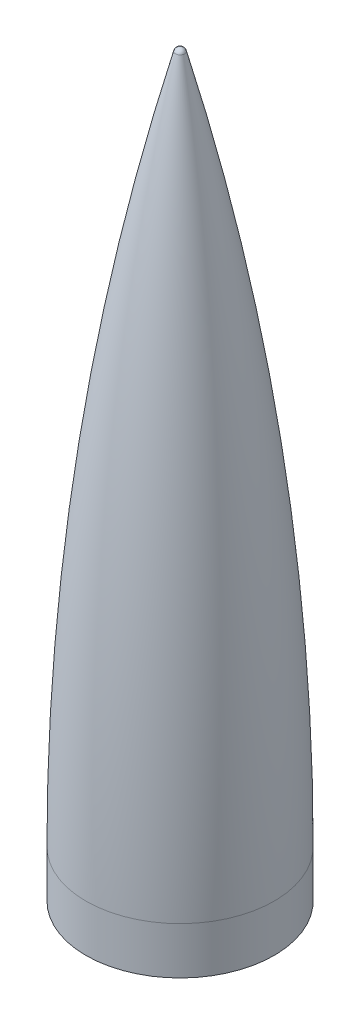
SolidWorks part; units mm, degrees
ref_plane "Front Plane" through (0, 0, 0) normal (0, 0, 1) x (1, 0, 0)
ref_plane "Top Plane" through (0, 0, 0) normal (0, 1, 0) x (1, 0, 0)
ref_plane "Right Plane" through (0, 0, 0) normal (1, 0, 0) x (0, 0, -1)
sketch "Sketch2" plane through (0, 0, 0) normal (0, 0, 1) x (1, 0, 0)
  line L0 (40, 0) -> (40, -20)
  line L1 (0, 294.2738) -> (0, 0) construction
  line L2 (40, -20) -> (38, -20)
  line L3 (38, -20) -> (38, 0)
  line L4 (0, 294.2738) -> (0, 292.2738)
  line L5 (0, 300) -> (0, 294.2738) construction
  line L6 (0, 300) -> (0, 294.2738) construction
  arc A0 (40, 0) -> (1.9335, 292.7853) centre (-1105, 0) ccw
  arc A1 (38, 0) -> (0, 292.2738) centre (-1105, 0) ccw
  arc A2 (38, 0) -> (-1.9301, 299.476) centre (-1105, 0) ccw construction
  arc A3 (1.9335, 292.7853) -> (0, 294.2738) centre (0, 292.2738) ccw
  arc A4 (1.9335, 292.7853) -> (0, 300) centre (-1105, 0) ccw construction
  arc A5 (40, 0) -> (0, 300) centre (-1105, 0) ccw construction
  point P13 (0, 294.2738)
  dimension "D1" = 40
  dimension "D2" = 20
  dimension "D3" = 300
  dimension "D4" = 2
revolve "Revolve1" add sketch "Sketch2" angle 360 about L1
